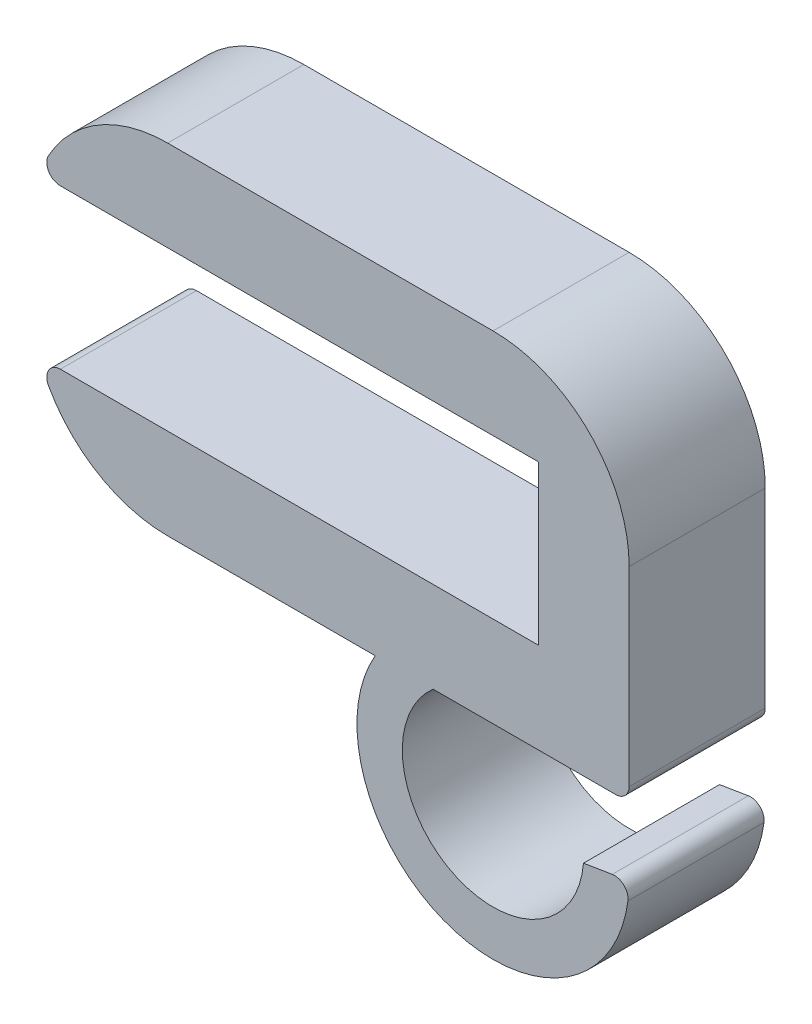
SolidWorks part; units mm, degrees
ref_plane "Płaszczyzna przednia" through (0, 0, 0) normal (0, 0, 1) x (1, 0, 0)
ref_plane "Płaszczyzna górna" through (0, 0, 0) normal (0, 1, 0) x (1, 0, 0)
ref_plane "Płaszczyzna prawa" through (0, 0, 0) normal (1, 0, 0) x (0, 0, -1)
sketch "Szkic1" plane through (0, 0, 0) normal (0, 0, 1) x (1, 0, 0)
  line L1 (0, 0) -> (13, 0)
  line L2 (0, 0) -> (0, 7.5)
  line L3 (0, 7.5) -> (13, 7.5)
  line L4 (13, 0) -> (13, 7.5)
  point P5 (0, 0)
extrude "Dodanie-wyciągnięcie1" add sketch "Szkic1" along normal blind 3 contours L3 L4 L1 L2
sketch "Szkic2" plane through (0, 0, 3) normal (0, 0, 1) x (1, 0, 0)
  line L0 (0, 0) -> (0, 7.5) construction
  line L1 (0, 5.5) -> (11, 5.5)
  line L2 (0, 5.5) -> (0, 2)
  line L3 (0, 2) -> (11, 2)
  line L4 (11, 5.5) -> (11, 2)
  point P6 (0, 0)
  point P7 (0, 0)
  point P8 (0, 0)
extrude "Wytnij-wyciągnięcie1" cut sketch "Szkic2" against normal blind 3
fillet "Zaokrąglenie1" radius 3 3 edges at (13, 7.5, 1.5) (0, 0, 1.5) (0, 7.5, 1.5)
sketch "Szkic3" plane through (0, 0, 3) normal (0, 0, 1) x (1, 0, 0)
  circle A0 centre (10, -1.5) radius 2
  circle A1 centre (10, -1.5) radius 3
extrude "Dodanie-wyciągnięcie2" add sketch "Szkic3" against normal blind 3
sketch "Szkic4" plane through (0, 0, 3) normal (0, 0, 1) x (1, 0, 0)
  line L0 (8.6771, 0) -> (11.3229, 0) construction
  line L1 (10, 0) -> (13, 0)
  line L2 (10, 0) -> (10, -1.9909)
  line L3 (10, -1.9909) -> (13, -1.5)
  line L4 (13, 0) -> (13, -1.5)
extrude "Wytnij-wyciągnięcie2" cut sketch "Szkic4" against normal blind 3
fillet "Zaokrąglenie2" radius 0.3 4 edges at (0, 2, 1.5) (0, 5.5, 1.5) (13, -1.5, 1.5) (13, 0, 1.5)
